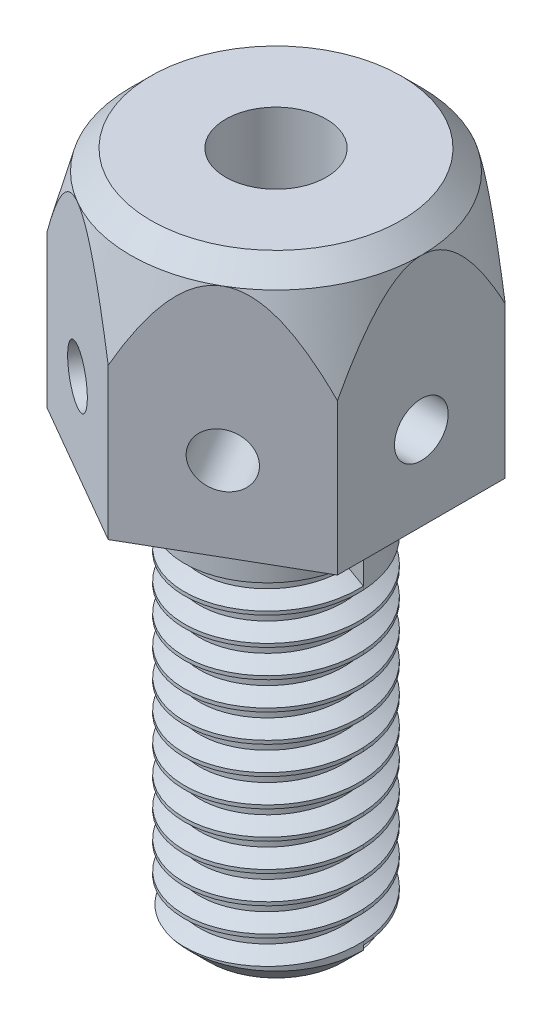
SolidWorks part; units mm, degrees
ref_plane "Front Plane" through (0, 0, 0) normal (0, 0, 1) x (1, 0, 0)
ref_plane "Top Plane" through (0, 0, 0) normal (0, 1, 0) x (1, 0, 0)
ref_plane "Right Plane" through (0, 0, 0) normal (1, 0, 0) x (0, 0, -1)
sketch "Sketch1" plane through (0, 0, 0) normal (0, 1, 0) x (1, 0, 0)
  circle A0 centre (0, 0) radius 3.302
  dimension "D1" = 6.604
extrude "Boss-Extrude1" add sketch "Sketch1" along normal blind 15.748
chamfer "Chamfer1" distance 0.762 angle 45 1 edges at (0, 0, 3.302)
thread "Thread2" pitch 1.0583 method cut profile "Thread Profile2" start angle 0, offset 0, length 12.7, pitch 1.0583, diameter 6.604
ref_plane "Plane2" through (3.302, 0, 0) normal (0, 0, 1) x (1, 0, 0)
sketch "Thread Profile2" plane through (3.302, 0, 0) normal (0, 0, 1) x (1, 0, 0)
  line L0 (0, 0) -> (0, 1.0583) construction
  line L11 (0, 0) -> (0, 0.926)
  line L12 (0, 0.926) -> (-0.5728, 0.5953)
  line L13 (-0.5728, 0.5953) -> (-0.5728, 0.3307)
  line L15 (-0.5728, 0.3307) -> (0, 0)
  line L17 (-0.5728, 0.463) -> (0, 0.463) construction
  point P2 (0, 0)
  dimension "Pitch" = 1.0583
  dimension "Profile_Angle" = 60
  dimension "Profile_Land" = 0.2646
  dimension "Profile_Height" = 0.5728
sketch "Sketch7" plane through (0, 15.748, 0) normal (0, 1, 0) x (1, 0, 0)
  line L1 (0, 6.35) -> (-5.4993, 3.175)
  line L2 (-5.4993, 3.175) -> (-5.4993, -3.175)
  line L3 (-5.4993, -3.175) -> (0, -6.35)
  line L4 (0, -6.35) -> (5.4993, -3.175)
  line L5 (5.4993, -3.175) -> (5.4993, 3.175)
  line L6 (5.4993, 3.175) -> (0, 6.35)
  circle A0 centre (0, 0) radius 5.4993 construction
  dimension "D1" = 12.7
extrude "Boss-Extrude2" add sketch "Sketch7" along normal blind 8.89
sketch "Sketch8" plane through (0, 24.638, 0) normal (0, 1, 0) x (1, 0, 0)
  circle A0 centre (0, 0) radius 1.905
  dimension "D1" = 3.81
extrude "Cut-Extrude1" cut sketch "Sketch8" against normal blind 8.89
sketch "Sketch14" plane through (0, 24.638, 0) normal (0, 1, 0) x (1, 0, 0)
  circle A0 centre (0, 0) radius 5.4993
extrude "Boss-Extrude3" add sketch "Sketch14" along normal blind 0.762
chamfer "Chamfer5" distance 0.762 angle 45 1 edges at (0, 25.4, 5.4993)
sketch "Sketch15" plane through (0, 0, 0) normal (1, 0, 0) x (0, 0, -1)
  line L0 (6.5795, 24.638) -> (5.4993, 24.638)
  line L1 (5.4993, 24.638) -> (6.5795, 20.6066)
  line L2 (6.5795, 20.6066) -> (6.5795, 24.638)
  point P3 (6.5795, 25.4)
  dimension "D1" = 75
sketch "Sketch16" plane through (0, 24.638, 0) normal (0, 1, 0) x (1, 0, 0)
  circle A0 centre (0, 0) radius 5.4993
sweep "Cut-Sweep2" cut profiles "Sketch15" path "Sketch16"
sketch "Sketch17" plane through (-5.4993, 0, 0) normal (-1, 0, 0) x (0, 0, 1)
  line L0 (-3.302, 15.748) -> (3.302, 15.748) construction
  line L1 (-3.175, 15.748) -> (3.175, 15.748) construction
  circle A0 centre (0, 18.9257) radius 1.016
  point P6 (0, 15.748)
  dimension "D1" = 2.032
  dimension "D2" = 3.1777
extrude "Cut-Extrude2" cut sketch "Sketch17" against normal blind 6.35
pattern_circular "CirPattern1" count 6 over 360 about axis through (0, 25.4, 0) along (0, 1, 0) of "Cut-Extrude2"
sketch "Sketch18" plane through (0, 25.4, 0) normal (0, 1, 0) x (1, 0, 0)
  circle A0 centre (0, 0) radius 1.905
  dimension "D1" = 3.81
extrude "Cut-Extrude3" cut sketch "Sketch18" against normal blind 7.874
